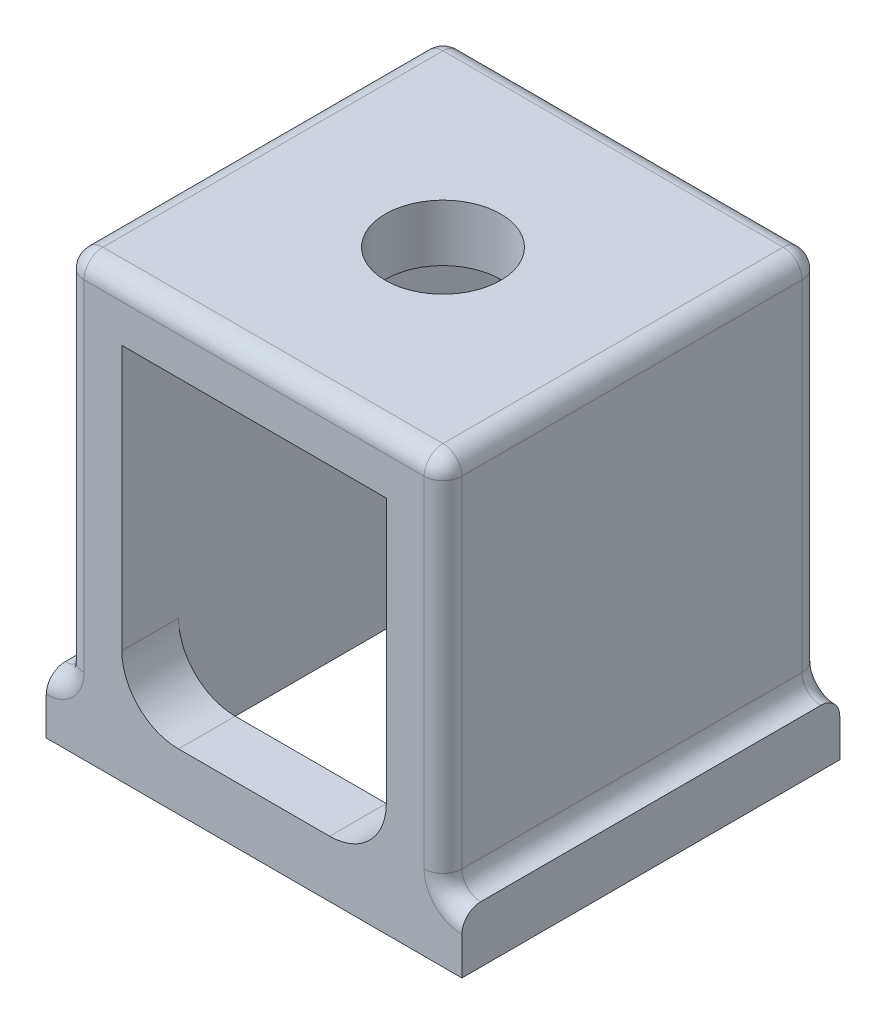
SolidWorks part; units mm, degrees
ref_plane "前视基准面" through (0, 0, 0) normal (0, 0, 1) x (1, 0, 0)
ref_plane "上视基准面" through (0, 0, 0) normal (0, 1, 0) x (1, 0, 0)
ref_plane "右视基准面" through (0, 0, 0) normal (1, 0, 0) x (0, 0, -1)
sketch "草图1" plane through (0, 0, 0) normal (0, 1, 0) x (1, 0, 0)
  line L1 (-7, 10) -> (7, 10)
  line L2 (-7, 10) -> (-7, -10)
  line L3 (-7, -10) -> (7, -10)
  line L4 (7, 10) -> (7, -10)
  line L5 (-7, 10) -> (7, -10) construction
  line L6 (-7, -10) -> (7, 10) construction
  circle A0 centre (0, 0) radius 3.05
  dimension "D1" = 6.1
  dimension "D2" = 20
  dimension "D3" = 14
extrude "凸台-拉伸1" add sketch "草图1" along normal blind 3
sketch "草图2" plane through (0, 0, 10) normal (0, 0, 1) x (1, 0, 0)
  line L0 (-7, 3) -> (-7, 0) construction
  line L1 (-7, 3) -> (-7, 0)
  line L2 (-7, 0) -> (-7, -20)
  line L3 (-7, -20) -> (-11, -20)
  line L4 (-10, 3) -> (-10, 0)
  line L5 (-10, 0) -> (-10, -17)
  line L6 (-10, -17) -> (-11, -17)
  line L7 (-11, -17) -> (-11, -20)
  line L8 (-10, 3) -> (-7, 3)
  line L9 (0, 15.9205) -> (0, -17.3192) construction
  line L10 (10, 3) -> (10, 0)
  line L11 (10, 0) -> (10, -17)
  line L12 (10, -17) -> (11, -17)
  line L13 (11, -17) -> (11, -20)
  line L14 (7, -20) -> (11, -20)
  line L15 (7, 0) -> (7, -20)
  line L16 (7, 3) -> (7, 0)
  line L17 (10, 3) -> (7, 3)
  point P14 (-9.7, -4.4973)
  dimension "D1" = 3
  dimension "D2" = 22
  dimension "D3" = 20
extrude "凸台-拉伸2" add sketch "草图2" against normal up to surface (20 mm away) up to face at (0, 1.5, -10)
sketch "草图4" plane through (0, -20, 0) normal (0, -1, 0) x (1, 0, 0)
  line L0 (-11, -10) -> (-11, 10) construction
  line L1 (-11, 10) -> (11, 10)
  line L2 (-11, 10) -> (-11, -10)
  line L3 (-11, -10) -> (11, -10)
  line L4 (11, 10) -> (11, -10)
  line L5 (-11, 10) -> (11, -10) construction
  line L6 (-11, -10) -> (11, 10) construction
  line L9 (-7, 7) -> (7, 7)
  line L10 (-7, 7) -> (-7, -7)
  line L11 (-7, -7) -> (7, -7)
  line L12 (7, 7) -> (7, -7)
  line L13 (-7, 7) -> (7, -7) construction
  line L14 (-7, -7) -> (7, 7) construction
  point P0 (0, 0)
  point P8 (-7, -7.3665)
  point P9 (-11, -10)
  point P10 (0, 0)
  dimension "D1" = 3
  dimension "D3" = 4
extrude "凸台-拉伸4" add sketch "草图4" against normal up to surface (3 mm away) up to face at (10.5, -17, 0)
fillet "圆角2" radius 1 12 edges at (-10, 3, 0) (0, 3, -10) (10, 3, 0) (0, 3, 10) (-10.5, -17, 10) (-10.5, -17, -10) (-10, -17, 0) (-10, -7, 10) (-10, -7, -10) (10, -7, 10) (10, -7, -10) (10, -17, 0)
fillet "圆角3" radius 3 4 edges at (-7, -17, -8.5) (7, -17, -8.5) (7, -17, 8.5) (-7, -17, 8.5)
